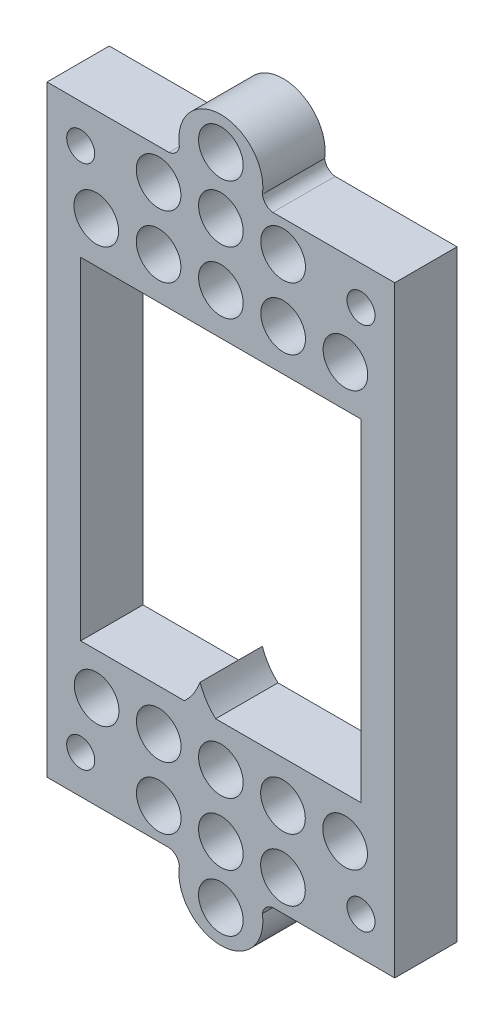
SolidWorks part; units mm, degrees
ref_plane "Front Plane" through (0, 0, 0) normal (0, 0, 1) x (1, 0, 0)
ref_plane "Top Plane" through (0, 0, 0) normal (0, 1, 0) x (1, 0, 0)
ref_plane "Right Plane" through (0, 0, 0) normal (1, 0, 0) x (0, 0, -1)
sketch "Sketch1" plane through (0, 0, 0) normal (0, 0, 1) x (1, 0, 0)
  line L0 (-13.5, -9.4654) -> (-2, -9.4654) construction
  line L1 (-16.75, 29) -> (-5, 29)
  line L2 (-16.75, 29) -> (-16.75, -29)
  line L3 (-16.75, -29) -> (-5, -29)
  line L4 (16.75, 29) -> (16.75, -29)
  line L5 (-13.5, 16) -> (13.5, 16)
  line L6 (-13.5, 16) -> (-13.5, -16)
  line L7 (-13.5, -16) -> (-3.5, -16)
  line L8 (13.5, 16) -> (13.5, -16)
  line L9 (-1.397, -14.9459) -> (-2.6159, -14.9374) construction
  line L10 (-1.15, -15.7286) -> (-2.85, -15.7286) construction
  line L11 (-2, -16) -> (-2, -13.7) construction
  line L12 (-0.5, -16) -> (13.5, -16)
  line L13 (-3.5, -16) -> (-0.5, -16) construction
  line L14 (-19.5, 29.3) -> (19.5, 29.3) construction
  line L15 (-19.5, 29.3) -> (-19.5, -29.3) construction
  line L16 (-19.5, -29.3) -> (19.5, -29.3) construction
  line L17 (19.5, 29.3) -> (19.5, -29.3) construction
  line L18 (-4, 30) -> (4, 30) construction
  line L19 (-5, 27.5542) -> (5, 27.5542) construction
  line L20 (0, 0) -> (4.3335, 0) construction
  line L21 (5, 29) -> (16.75, 29)
  line L22 (5, -29) -> (16.75, -29)
  arc A0 (-3.5, -16) -> (-2, -13.7) centre (-7.6154, -11.6769) ccw
  arc A1 (-0.5, -16) -> (-2, -13.7) centre (3.1751, -11.9641) cw
  circle A2 centre (-13.5, 25.3) radius 1.35
  circle A4 centre (13.5, -25.3) radius 1.35
  circle A5 centre (-13.5, -25.3) radius 1.35
  circle A6 centre (13.5, 25.3) radius 1.35
  arc A7 (-4, 30) -> (4, 30) centre (0, 30.6158) cw
  circle A8 centre (0, 31.5) radius 2.15
  arc A9 (-4, 30) -> (-5, 29) centre (-5.1229, 30.1229) cw
  arc A10 (4, 30) -> (5, 29) centre (5.1511, 30.1511) ccw
  arc A11 (4, -30) -> (5, -29) centre (5.1511, -30.1511) cw
  arc A12 (-4, -30) -> (-5, -29) centre (-5.1229, -30.1229) ccw
  circle A13 centre (0, -31.5) radius 2.15
  arc A15 (-4, -30) -> (4, -30) centre (0, -30.6158) ccw
  point P10 (-16.75, 0)
  point P11 (0, 16)
  point P12 (-13.5, 0)
  point P21 (-2, -15.7286)
  point P29 (19.5, 0)
  point P30 (0, 29.3)
  point P37 (-2, -16)
  point P39 (0, 30)
  point P46 (0, 27.5542)
  point P64 (-2, -16)
  point P65 (-2.6113, -14.9459)
  point P66 (-2.6159, -14.9459)
  dimension "D8" = 2.7
  dimension "D22" = 4.3
  dimension "D23" = 2.5
  dimension "D1" = 27
  dimension "D2" = 33.5
  dimension "D3" = 58
  dimension "D4" = 32
  dimension "D5" = 11.5
  dimension "D6" = 3
  dimension "D7" = 2.3
  dimension "D9" = 58.6
  dimension "D10" = 39
  dimension "D11" = 6
  dimension "D12" = 4
  dimension "D13" = 4
  dimension "D14" = 6
  dimension "D15" = 6
  dimension "D16" = 6
  dimension "D17" = 4
  dimension "D18" = 4
  dimension "D19" = 8
  dimension "D20" = 1
  dimension "D21" = 10
extrude "Boss-Extrude1" add sketch "Sketch1" along normal blind 6
sketch "Sketch2" plane through (0, 0, 6) normal (0, 0, 1) x (1, 0, 0)
  line L2 (-13.5, -16) -> (-3.5, -16) construction
  line L3 (13.5, 16) -> (-13.5, 16) construction
  circle A0 centre (-12, 20) radius 2.15
  circle A1 centre (-6, 20) radius 2.15
  circle A2 centre (0, 20) radius 2.15
  circle A3 centre (6, 20) radius 2.15
  circle A4 centre (12, 20) radius 2.15
  circle A5 centre (-6, 26) radius 2.15
  circle A6 centre (0, 26) radius 2.15
  circle A7 centre (6, 26) radius 2.15
  circle A8 centre (-11.9673, -20) radius 2.15
  circle A9 centre (-5.9837, -20) radius 2.15
  circle A10 centre (0, -20) radius 2.15
  circle A11 centre (5.9837, -20) radius 2.15
  circle A12 centre (11.9673, -20) radius 2.15
  circle A13 centre (-5.9837, -26) radius 2.15
  circle A14 centre (0, -26) radius 2.15
  circle A15 centre (5.9837, -26) radius 2.15
  dimension "D1" = 4.3
  dimension "D5" = 4.3
  dimension "D11" = 4.3
  dimension "D12" = 4.3
  dimension "D13" = 4.3
  dimension "D14" = 4.3
  dimension "D15" = 4.3
  dimension "D16" = 4.3
  dimension "D2" = 4
  dimension "D3" = 4
  dimension "D6" = 6
  dimension "D10" = 6
  dimension "D4" = 5
  dimension "D9" = 5
extrude "Cut-Extrude1" cut sketch "Sketch2" against normal blind 4.2
